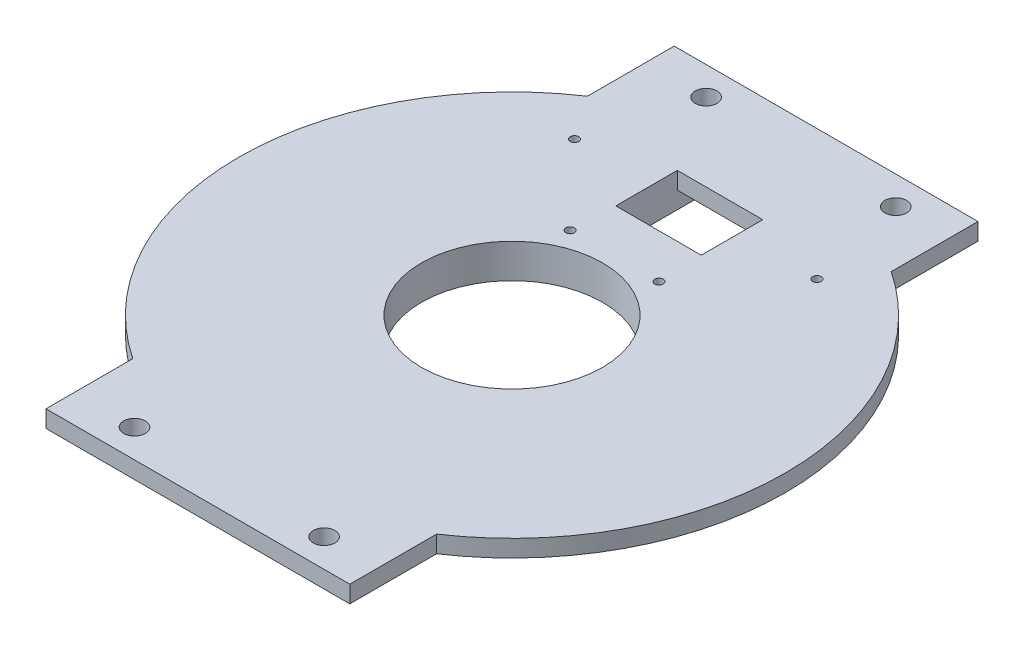
SolidWorks part; units mm, degrees
ref_plane "Front Plane" through (0, 0, 0) normal (0, 0, 1) x (1, 0, 0)
ref_plane "Top Plane" through (0, 0, 0) normal (0, 1, 0) x (1, 0, 0)
ref_plane "Right Plane" through (0, 0, 0) normal (1, 0, 0) x (0, 0, -1)
sketch "Sketch1" plane through (0, 0, 0) normal (0, 1, 0) x (1, 0, 0)
  circle A0 centre (0, 0) radius 26.5
  circle A1 centre (0, 0) radius 69
  dimension "D1" = 53
  dimension "D2" = 138
extrude "Boss-Extrude1" add sketch "Sketch1" along normal blind 10
sketch "Sketch2" plane through (0, 0, 0) normal (0, -1, 0) x (1, 0, 0)
  line L0 (0, 0) -> (-13, -30) construction
  line L1 (-8.7574, -30) -> (-13, -34.2426)
  line L2 (-8.7574, -30) -> (-13, -25.7574)
  line L3 (-13, -25.7574) -> (-17.2426, -30)
  line L4 (-13, -34.2426) -> (-17.2426, -30)
  line L5 (-8.7574, -30) -> (-17.2426, -30) construction
  line L6 (-13, -25.7574) -> (-13, -34.2426) construction
  line L7 (17.2426, -30) -> (13, -34.2426)
  line L8 (17.2426, -30) -> (13, -25.7574)
  line L9 (13, -25.7574) -> (8.7574, -30)
  line L10 (13, -34.2426) -> (8.7574, -30)
  line L11 (17.2426, -30) -> (8.7574, -30) construction
  line L12 (13, -25.7574) -> (13, -34.2426) construction
  line L13 (0, 0) -> (13, -30) construction
  line L14 (-35.46, -53.7582) -> (-13, -30) construction
  line L15 (-31.2174, -53.7582) -> (-35.46, -58.0009)
  line L16 (-31.2174, -53.7582) -> (-35.46, -49.5156)
  line L17 (-35.46, -49.5156) -> (-39.7026, -53.7582)
  line L18 (-35.46, -58.0009) -> (-39.7026, -53.7582)
  line L19 (-31.2174, -53.7582) -> (-39.7026, -53.7582) construction
  line L20 (-35.46, -49.5156) -> (-35.46, -58.0009) construction
  line L21 (39.7026, -53.7582) -> (35.46, -58.0009)
  line L22 (39.7026, -53.7582) -> (35.46, -49.5156)
  line L23 (35.46, -49.5156) -> (31.2174, -53.7582)
  line L24 (35.46, -58.0009) -> (31.2174, -53.7582)
  line L25 (39.7026, -53.7582) -> (31.2174, -53.7582) construction
  line L26 (35.46, -49.5156) -> (35.46, -58.0009) construction
  line L27 (13, -30) -> (35.46, -53.7582) construction
  point P0 (13, -30)
  point P4 (-13, -30)
  point P11 (35.46, -53.7582)
  point P13 (-35.46, -53.7582)
  dimension "D1" = 26
  dimension "D2" = 30
  dimension "D3" = 6
  dimension "D4" = 64.4
  dimension "D5" = 64.4
  dimension "D6" = 70.92
  dimension "D7" = 6
extrude "Cut-Extrude1" cut sketch "Sketch2" against normal blind 4.5 contours L4 L1 L2 L3 | L18 L15 L16 L17 | L10 L7 L8 L9 | L24 L21 L22 L23 region at (-13, 0, -30) region at (13, 0, -30) region at (-35.46, 0, -53.7582) region at (35.46, 0, -53.7582)
sketch "Sketch3" plane through (0, 0, 0) normal (0, -1, 0) x (1, 0, 0)
  line L1 (12.5, -60.875) -> (-12.5, -60.875)
  line L2 (12.5, -60.875) -> (12.5, -42.875)
  line L3 (12.5, -42.875) -> (-12.5, -42.875)
  line L4 (-12.5, -60.875) -> (-12.5, -42.875)
  line L5 (12.5, -60.875) -> (-12.5, -42.875) construction
  line L6 (12.5, -42.875) -> (-12.5, -60.875) construction
  point P0 (0, -51.875)
  dimension "D1" = 51.875
  dimension "D2" = 18
  dimension "D3" = 25
extrude "Cut-Extrude2" cut sketch "Sketch3" against normal through all
sketch "Sketch4" plane through (0, 0, 0) normal (0, -1, 0) x (1, 0, 0)
  line L0 (31.2174, -53.7582) -> (35.46, -58.0009) construction
  line L1 (35.46, -58.0009) -> (39.7026, -53.7582) construction
  line L2 (39.7026, -53.7582) -> (35.46, -49.5156) construction
  line L3 (35.46, -49.5156) -> (31.2174, -53.7582) construction
  line L4 (8.7574, -30) -> (13, -34.2426) construction
  line L5 (13, -34.2426) -> (17.2426, -30) construction
  line L6 (17.2426, -30) -> (13, -25.7574) construction
  line L7 (13, -25.7574) -> (8.7574, -30) construction
  line L8 (-39.7026, -53.7582) -> (-35.46, -58.0009) construction
  line L9 (-35.46, -58.0009) -> (-31.2174, -53.7582) construction
  line L10 (-31.2174, -53.7582) -> (-35.46, -49.5156) construction
  line L11 (-35.46, -49.5156) -> (-39.7026, -53.7582) construction
  line L12 (-17.2426, -30) -> (-13, -34.2426) construction
  line L13 (-13, -34.2426) -> (-8.7574, -30) construction
  line L14 (-8.7574, -30) -> (-13, -25.7574) construction
  line L15 (-13, -25.7574) -> (-17.2426, -30) construction
  line L16 (31.2174, -53.7582) -> (35.46, -58.0009) construction
  line L17 (35.46, -58.0009) -> (39.7026, -53.7582) construction
  line L18 (39.7026, -53.7582) -> (35.46, -49.5156) construction
  line L19 (35.46, -49.5156) -> (31.2174, -53.7582) construction
  line L20 (8.7574, -30) -> (13, -34.2426) construction
  line L21 (13, -34.2426) -> (17.2426, -30) construction
  line L22 (17.2426, -30) -> (13, -25.7574) construction
  line L23 (13, -25.7574) -> (8.7574, -30) construction
  line L24 (-39.7026, -53.7582) -> (-35.46, -58.0009) construction
  line L25 (-35.46, -58.0009) -> (-31.2174, -53.7582) construction
  line L26 (-31.2174, -53.7582) -> (-35.46, -49.5156) construction
  line L27 (-35.46, -49.5156) -> (-39.7026, -53.7582) construction
  line L28 (-17.2426, -30) -> (-13, -34.2426) construction
  line L29 (-13, -34.2426) -> (-8.7574, -30) construction
  line L30 (-8.7574, -30) -> (-13, -25.7574) construction
  line L31 (-13, -25.7574) -> (-17.2426, -30) construction
  circle A0 centre (-13, -30) radius 1.25
  circle A1 centre (13, -30) radius 1.25
  circle A2 centre (-35.46, -53.7582) radius 1.25
  circle A3 centre (35.46, -53.7582) radius 1.25
  dimension "D1" = 2.5
extrude "Cut-Extrude3" cut sketch "Sketch4" against normal through all
sketch "Sketch5" plane through (0, 0, 0) normal (0, -1, 0) x (1, 0, 0)
  line L0 (-43, -46.7253) -> (-12.5, -42.875) construction
  line L1 (12.5, -42.875) -> (43, -46.7253) construction
  line L2 (-44.9013, 44.9013) -> (-12.5, -42.875) construction
  line L3 (12.5, -42.875) -> (44.9013, 44.9013) construction
  circle A2 centre (-44.9013, 44.9013) radius 1.9
  circle A3 centre (44.9013, 44.9013) radius 1.9
  circle A4 centre (-43, -46.7253) radius 1.9
  circle A5 centre (43, -46.7253) radius 1.9
  dimension "D1" = 89.8026
  dimension "D4" = 3.8
  dimension "D5" = 63.5
  dimension "D7" = 86
  dimension "D2" = 63.5
  dimension "D3" = 63.5
  dimension "D6" = 63.5
extrude "Boss-Extrude2" add sketch "Sketch5" along normal blind 3.5 contours A3 | A2 | A4 | A5 region at (44.9013, 0, 44.9013)
sketch "Sketch6" plane through (0, 10, 0) normal (0, 1, 0) x (1, 0, 0)
  line L0 (-5.5, 0) -> (5.5, 0) construction
  line L1 (-44.45, 66.5146) -> (44.45, 66.5146) construction
  line L2 (-44.45, 66.5146) -> (-44.45, 91.9146)
  line L3 (-44.45, 91.9146) -> (44.45, 91.9146)
  line L4 (44.45, 66.5146) -> (44.45, 91.9146)
  line L5 (-44.45, -66.5146) -> (44.45, -66.5146) construction
  line L6 (44.45, -66.5146) -> (44.45, -91.9146)
  line L7 (-44.45, -66.5146) -> (-44.45, -91.9146)
  line L8 (-44.45, -91.9146) -> (44.45, -91.9146)
  line L9 (-26.8356, 91.9146) -> (-26.8356, 83.6397) construction
  line L10 (-26.8356, 83.6397) -> (-26.8356, 75.3648) construction
  circle A0 centre (0, 0) radius 80
  circle A1 centre (-26.8356, 83.6397) radius 3.175
  circle A2 centre (28.6621, 83.6397) radius 3.175
  circle A3 centre (28.6621, -83.6397) radius 3.175
  circle A4 centre (-26.8356, -83.6397) radius 3.175
  point P8 (0, 66.5146)
  circle M14 centre (0, 0) radius 69
  dimension "D1" = 88.9
  dimension "D2" = 160
  dimension "D4" = 6.35
  dimension "D3" = 25.4
extrude "Boss-Extrude3" add sketch "Sketch6" against normal blind 5 contours A0 M14 | A0 L4 L3 L2 | A0 L7 L8 L6 region at (-0.0419, 10, -83.2926) region at (0, 10, -77.7373) region at (-0.0419, 10, 83.2926)
chamfer "Chamfer1" distance 1 angle 20 4 edges at (43, -3.5, -48.6253) (44.9013, -3.5, 43.0013) (-43, -3.5, -48.6253) (-44.9013, -3.5, 43.0013) first distance on face at (43, -3.5, -48.6253) first distance on face at (44.9013, -3.5, 43.0013) first distance on face at (-43, -3.5, -48.6253) first distance on face at (-44.9013, -3.5, 43.0013)
sketch "Sketch7" plane through (0, 0, 0) normal (0, -1, 0) x (1, 0, 0)
  line L1 (-12.5, -60.875) -> (12.5, -60.875)
  line L2 (-12.5, -60.875) -> (-12.5, -69)
  line L3 (-12.5, -69) -> (12.5, -69)
  line L4 (12.5, -60.875) -> (12.5, -69)
  circle A0 centre (0, 0) radius 69 construction
extrude "Cut-Extrude4" cut sketch "Sketch7" against normal up to surface (5 mm away) up to face at (0, 5, 69)
sketch "Sketch8" plane through (0, 0, 0) normal (0, -1, 0) x (1, 0, 0)
  line L0 (0, 0) -> (-66.0526, 19.9514)
  line L1 (0, 0) -> (-65.1681, -22.6743)
  line L2 (0, 0) -> (0, 18.7046) construction
  line L3 (0, 0) -> (65.1681, -22.6743)
  line L4 (0, 0) -> (66.0526, 19.9514)
  circle A0 centre (0, 0) radius 61.6
  arc A1 (12.5, -67.8583) -> (-12.5, -67.8583) centre (0, 0) ccw construction
  arc A2 (12.5, -67.8583) -> (-12.5, -67.8583) centre (0, 0) ccw
  circle A3 centre (-44.9013, 44.9013) radius 1.9 construction
  circle A4 centre (44.9013, 44.9013) radius 1.536 construction
  circle A5 centre (-44.9013, 44.9013) radius 1.536
  circle A6 centre (-44.9013, 44.9013) radius 1.536
  circle A7 centre (43, -46.7253) radius 1.536 construction
  circle A8 centre (-43, -46.7253) radius 1.536 construction
  circle A9 centre (44.9013, 44.9013) radius 1.536
  circle A10 centre (43, -46.7253) radius 1.536
  circle A11 centre (-43, -46.7253) radius 1.536
  arc M19 (12.5, -67.8583) -> (-12.5, -67.8583) centre (0, 0) ccw
  dimension "D1" = 0
  dimension "D2" = 30
  dimension "D3" = 30
extrude "Cut-Extrude5" cut sketch "Sketch8" against normal blind 2 contours A0 L0 L1 M19 | A0 L3 L4 M19 region at (-64.2865, 0, -1.334) region at (64.2865, 0, -1.334)
fillet "Fillet1" radius 5 1 edges at (0, 5, 69)
fillet "Fillet2" radius 2 6 edges at (61.8707, 2, -21.527) (61.5867, 2, -1.2779) (62.7104, 2, 18.9419) (-61.8707, 2, -21.527) (-61.5867, 2, -1.2779) (-62.7104, 2, 18.9419)
